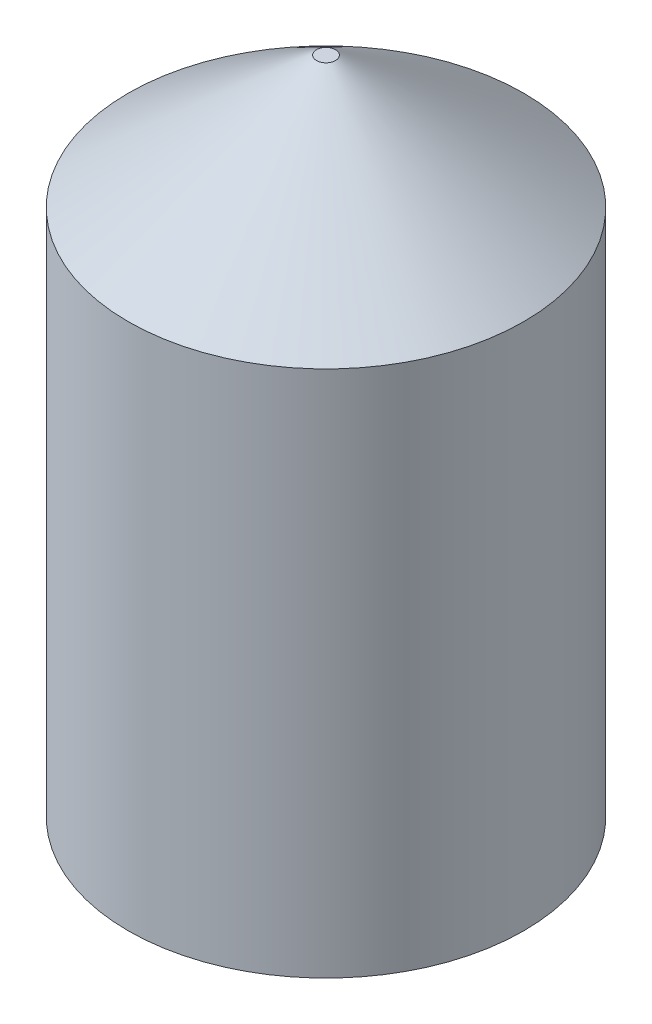
SolidWorks part; units mm, degrees
ref_plane "Front Plane" through (0, 0, 0) normal (0, 0, 1) x (1, 0, 0)
ref_plane "Top Plane" through (0, 0, 0) normal (0, 1, 0) x (1, 0, 0)
ref_plane "Right Plane" through (0, 0, 0) normal (1, 0, 0) x (0, 0, -1)
sketch "Sketch1" plane through (0, 0, 0) normal (0, 1, 0) x (1, 0, 0)
  circle A0 centre (0, 0) radius 30
  dimension "D1" = 60
extrude "Boss-Extrude1" add sketch "Sketch1" along normal blind 100
sketch "Sketch2" plane through (0, 0, 0) normal (0, -1, 0) x (1, 0, 0)
  circle A0 centre (0, 0) radius 2
extrude "Cut-Extrude1" cut sketch "Sketch2" against normal blind 20
chamfer "Chamfer1" distance 20 angle 55 1 edges at (0, 100, 30) first distance on face at (0, 100, 30)
